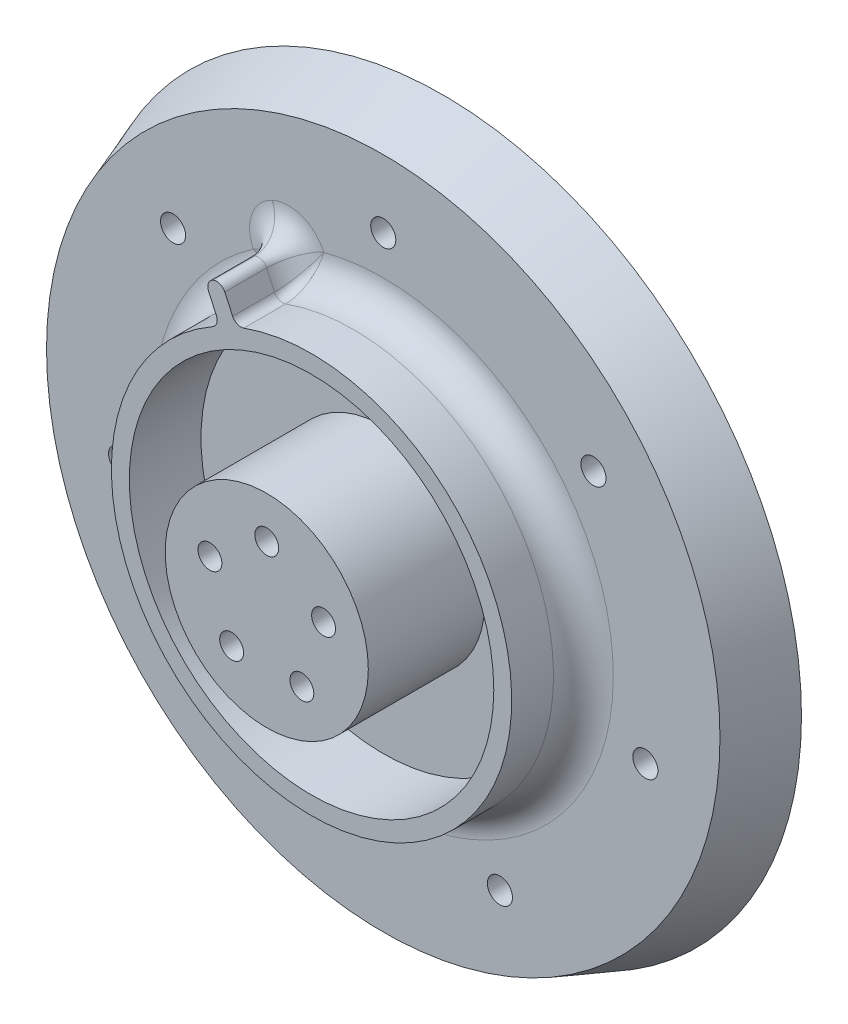
SolidWorks part; units mm, degrees
ref_plane "Plano frontal" through (0, 0, 0) normal (0, 0, 1) x (1, 0, 0)
ref_plane "Plano superior" through (0, 0, 0) normal (0, 1, 0) x (1, 0, 0)
ref_plane "Plano direito" through (0, 0, 0) normal (1, 0, 0) x (0, 0, -1)
sketch "Esboço1" plane through (0, 0, 0) normal (0, 0, 1) x (1, 0, 0)
  circle A0 centre (0, 0) radius 60
  dimension "D1" = 120
extrude "Ressalto-extrusão1" add sketch "Esboço1" along normal blind 10
sketch "Esboço2" plane through (0, 0, 10) normal (0, 0, 1) x (1, 0, 0)
  circle A0 centre (0, 0) radius 17
  dimension "D1" = 34
extrude "Ressalto-extrusão2" add sketch "Esboço2" along normal blind 19.5
sketch "Esboço3" plane through (0, 0, 10) normal (0, 0, 1) x (1, 0, 0)
  line L0 (-13.9923, 30.4379) -> (-16.4984, 35.8895) construction
  line L1 (-17.8613, 35.263) -> (-15.1355, 36.516)
  line L2 (-17.8613, 35.263) -> (-15.3411, 29.7809)
  line L3 (-15.1355, 36.516) -> (-12.6154, 31.0339)
  circle A0 centre (0, 0) radius 30.5
  arc A1 (-15.3411, 29.7809) -> (-12.6154, 31.0339) centre (0, 0) ccw
  point P9 (-16.4984, 35.8895)
  point P12 (-16.4984, 35.8895)
  dimension "D1" = 61
  dimension "D2" = 67
  dimension "D3" = 6
  dimension "D4" = 3
extrude "Ressalto-extrusão3" add sketch "Esboço3" along normal blind 12
sketch "Esboço4" plane through (0, 0, 10) normal (0, 0, 1) x (1, 0, 0)
  circle A0 centre (0, 45) radius 2.1
  circle A6 centre (35.1824, 28.057) radius 2.1
  circle A7 centre (43.8718, -10.0134) radius 2.1
  circle A8 centre (19.5248, -40.5436) radius 2.1
  circle A9 centre (-19.5248, -40.5436) radius 2.1
  circle A10 centre (-43.8718, -10.0134) radius 2.1
  circle A11 centre (-35.1824, 28.057) radius 2.1
  point P16 (0, 0)
  point P18 (0, 0)
  dimension "D1" = 4.2
  dimension "D2" = 45
  dimension "D3" = 7
extrude "Corte-extrusão1" cut sketch "Esboço4" against normal up to surface (10 mm away) up to face at (60, 0, 0)
chamfer "Chanfro1" distance 10 angle 20 1 edges at (60, 0, 10) first distance on face at (60, 0, 10)
sketch "Esboço5" plane through (0, 0, 29.5) normal (0, 0, 1) x (1, 0, 0)
  circle A0 centre (0, 10) radius 2
  circle A1 centre (9.5106, 3.0902) radius 2
  circle A2 centre (5.8779, -8.0902) radius 2
  circle A3 centre (-5.8779, -8.0902) radius 2
  circle A4 centre (-9.5106, 3.0902) radius 2
  point P14 (0, 0)
  dimension "D1" = 4
  dimension "D2" = 10
  dimension "D3" = 5
extrude "Corte-extrusão2" cut sketch "Esboço5" against normal up to surface (29.5 mm away) up to face at (2.1, 45, 0)
chamfer "Chanfro2" distance 3 angle 45 5 edges at (-3.8779, -8.0902, 0) (-7.5106, 3.0902, 0) (2, 10, 0) (11.5106, 3.0902, 0) (7.8779, -8.0902, 0)
fillet "Filete1" radius 1.5 4 edges at (-15.3411, 29.7809, 16) (-17.8613, 35.263, 16) (-15.1355, 36.516, 16) (-12.6154, 31.0339, 16)
fillet "Filete2" radius 5 7 edges at (-15.863, 29.9709, 10) (-16.5813, 32.4787, 10) (-17.2786, 35.0473, 10) (-15.3511, 35.9333, 10) (-13.8555, 33.7317, 10) (-12.4198, 31.5537, 10) (13.9923, -30.4379, 10)
